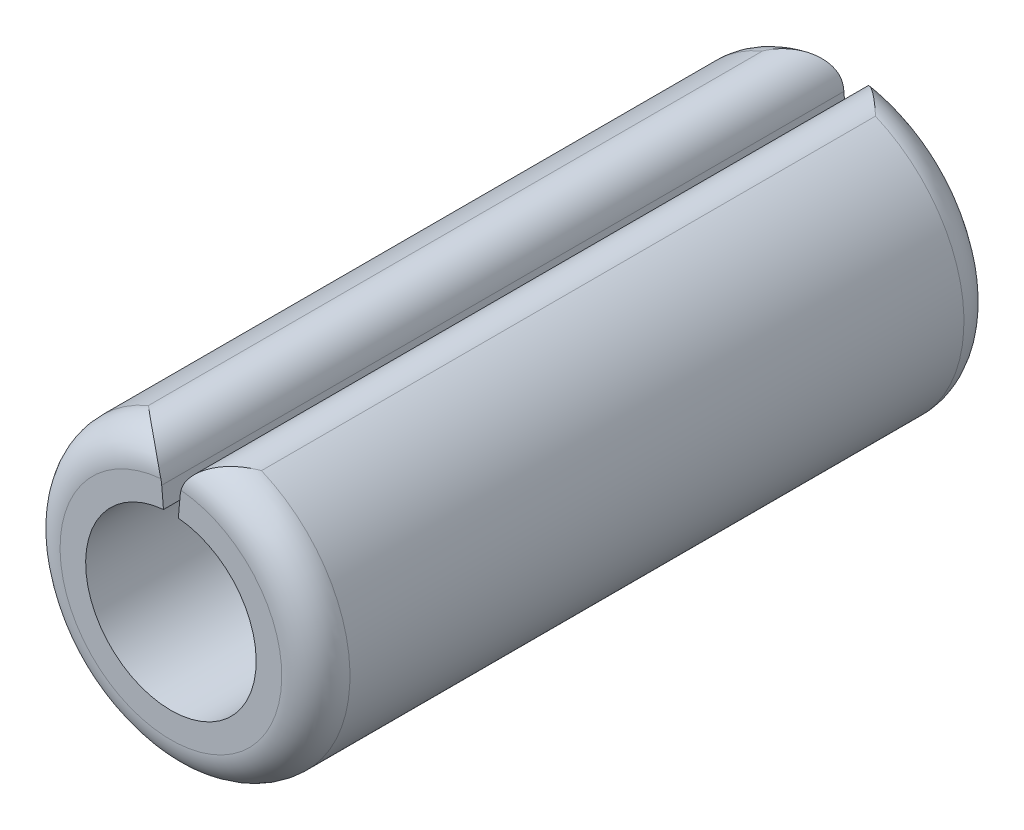
SolidWorks part; units mm, degrees
material "Plain Carbon Steel"
ref_plane "Front Plane" through (0, 0, 0) normal (0, 0, 1) x (1, 0, 0)
ref_plane "Top Plane" through (0, 0, 0) normal (0, 1, 0) x (1, 0, 0)
ref_plane "Right Plane" through (0, 0, 0) normal (1, 0, 0) x (0, 0, -1)
sketch "Sketch1" plane through (0, 0, 0) normal (0, 0, 1) x (1, 0, 0)
  line L0 (0, 0) -> (0, 19.3086) construction
  line L1 (0, 0) -> (-2.1412, 24.4738) construction
  line L2 (0, 0) -> (2.1412, 24.4738) construction
  line L3 (0.0741, 0.8468) -> (0.0436, 0.4981)
  line L4 (-0.0436, 0.4981) -> (-0.0741, 0.8468)
  arc A0 (-0.0741, 0.8468) -> (0.0741, 0.8468) centre (0, 0) ccw
  arc A1 (-0.0436, 0.4981) -> (0.0436, 0.4981) centre (0, 0) ccw
  dimension "D2" = 0.85
  dimension "D3" = 0.5
  dimension "D1" = 10
extrude "Boss-Extrude1" add sketch "Sketch1" along normal blind 2 and the other way blind 2
fillet "Fillet2" radius 0.2 4 edges at (0, -0.85, 2) (0, -0.85, -2) (0.0741, 0.8468, 0) (-0.0741, 0.8468, 0)
